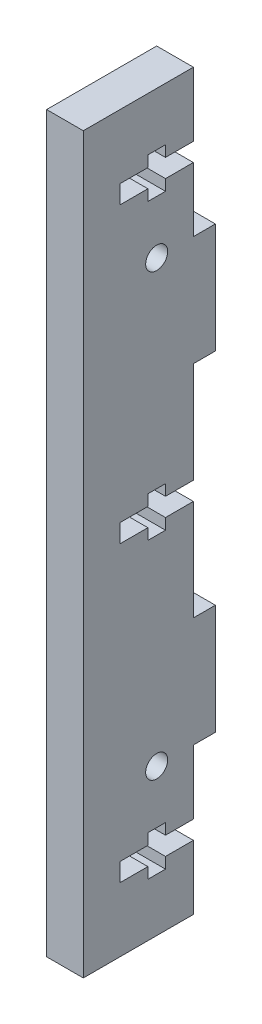
SolidWorks part; units mm, degrees
material "PMMA"
ref_plane "Front Plane" through (0, 0, 0) normal (0, 0, 1) x (1, 0, 0)
ref_plane "Top Plane" through (0, 0, 0) normal (0, 1, 0) x (1, 0, 0)
ref_plane "Right Plane" through (0, 0, 0) normal (1, 0, 0) x (0, 0, -1)
sketch "Schizzo1" plane through (0, 0, 0) normal (1, 0, 0) x (0, 0, -1)
  line L0 (-7.5, 50) -> (7.5, -50) construction
  line L1 (-7.5, 50) -> (7.5, 50)
  line L2 (-7.5, 50) -> (-7.5, -50)
  line L3 (-7.5, -50) -> (7.5, -50)
  line L4 (7.5, 50) -> (7.5, -50)
  point P4 (0, 0)
  dimension "D1" = 100
  dimension "D2" = 15
extrude "Estrusione-Estrusione1" add sketch "Schizzo1" along normal blind 5
sketch "Schizzo2" plane through (0, 0, -7.5) normal (0, 0, -1) x (-1, 0, 0)
  line L0 (-5, 0) -> (0, 0) construction
  line L1 (-5, 30) -> (0, 30)
  line L2 (-5, 30) -> (-5, 15)
  line L3 (-5, 15) -> (0, 15)
  line L4 (0, 30) -> (0, 15)
  line L5 (-5, -50) -> (-5, 50) construction
  line L7 (0, -50) -> (0, 50) construction
  line L8 (-5, -30) -> (-5, -15)
  line L9 (-5, -15) -> (0, -15)
  line L10 (0, -30) -> (0, -15)
  line L11 (-5, -30) -> (0, -30)
  dimension "D1" = 15
  dimension "D2" = 15
extrude "Estrusione-Estrusione2" add sketch "Schizzo2" along normal blind 3
sketch "Schizzo4" plane through (0, 0, 0) normal (1, 0, 0) x (0, 0, -1)
  line L0 (2.5, 50) -> (2.5, -50) construction
  line L1 (7.5, 50) -> (-7.5, 50) construction
  line L2 (-7.5, -50) -> (7.5, -50) construction
  line L3 (7.5, 30) -> (7.5, 50) construction
  line L4 (7.5, 0) -> (-7.5, 0) construction
  line L5 (7.5, -15) -> (7.5, 15) construction
  line L6 (-7.5, 50) -> (-7.5, -50) construction
  line L7 (7.5, 30) -> (7.5, 50) construction
  circle A1 centre (2.5, 30) radius 1.5
  circle A2 centre (2.5, -30) radius 1.5
  dimension "D3" = 20
  dimension "D1" = 5
extrude "Taglio-Estrusione2" cut sketch "Schizzo4" along direction (1, 0, 0) on the side of the normal through all
sketch "Schizzo5" plane through (5, 0, 0) normal (1, 0, 0) x (0, 0, -1)
  line L0 (-8.3871, 0) -> (1.6129, 0) construction
  line L1 (-2.5, 1.25) -> (1.3, 1.25)
  line L2 (1.3, 1.25) -> (1.3, 2.75)
  line L3 (1.3, 2.75) -> (3.7, 2.75)
  line L4 (3.7, 2.75) -> (3.7, 1.25)
  line L5 (3.7, 1.25) -> (7.5, 1.25)
  line L6 (7.5, 1.25) -> (7.5, -1.25)
  line L7 (7.5, -1.25) -> (3.7, -1.25)
  line L8 (3.7, -1.25) -> (3.7, -2.75)
  line L9 (3.7, -2.75) -> (1.3, -2.75)
  line L10 (1.3, -2.75) -> (1.3, -1.25)
  line L11 (1.3, -1.25) -> (-2.5, -1.25)
  line L12 (-2.5, -1.25) -> (-2.5, 1.25)
  line L13 (7.5, 0) -> (-7.5, 0) construction
  line L14 (7.5, -15) -> (7.5, 15) construction
  line L15 (-7.5, 50) -> (-7.5, -50) construction
  line L16 (-2.5, -38.75) -> (1.3, -38.75)
  line L17 (1.3, -38.75) -> (1.3, -37.25)
  line L18 (1.3, -37.25) -> (3.7, -37.25)
  line L19 (3.7, -37.25) -> (3.7, -38.75)
  line L20 (3.7, -38.75) -> (7.5, -38.75)
  line L21 (7.5, -38.75) -> (7.5, -41.25)
  line L22 (7.5, -41.25) -> (3.7, -41.25)
  line L23 (3.7, -41.25) -> (3.7, -42.75)
  line L24 (3.7, -42.75) -> (1.3, -42.75)
  line L25 (1.3, -42.75) -> (1.3, -41.25)
  line L26 (1.3, -41.25) -> (-2.5, -41.25)
  line L27 (-2.5, -41.25) -> (-2.5, -38.75)
  line L28 (7.5, 38.75) -> (7.5, 41.25)
  line L29 (3.7, 38.75) -> (7.5, 38.75)
  line L30 (3.7, 37.25) -> (3.7, 38.75)
  line L31 (1.3, 37.25) -> (3.7, 37.25)
  line L32 (1.3, 38.75) -> (1.3, 37.25)
  line L33 (-2.5, 38.75) -> (1.3, 38.75)
  line L34 (-2.5, 41.25) -> (-2.5, 38.75)
  line L35 (1.3, 41.25) -> (-2.5, 41.25)
  line L36 (1.3, 42.75) -> (1.3, 41.25)
  line L37 (3.7, 42.75) -> (1.3, 42.75)
  line L38 (3.7, 41.25) -> (3.7, 42.75)
  line L39 (7.5, 41.25) -> (3.7, 41.25)
  dimension "D1" = 5.5
  dimension "D2" = 2.5
  dimension "D3" = 1.25
  dimension "D4" = 2.75
  dimension "D5" = 2.4
  dimension "D6" = 10
  dimension "D7" = 2
  dimension "D8" = 1
extrude "Taglio-Estrusione3" cut sketch "Schizzo5" along direction (1, 0, 0) on the side against the normal through all
equation "\"Thickness5\"=5"
equation "\"D1@Estrusione-Estrusione1\"=\"Thickness5\""
equation "\"Thickness3\"=3"
equation "\"D1@Estrusione-Estrusione2\"=\"Thickness3\""
